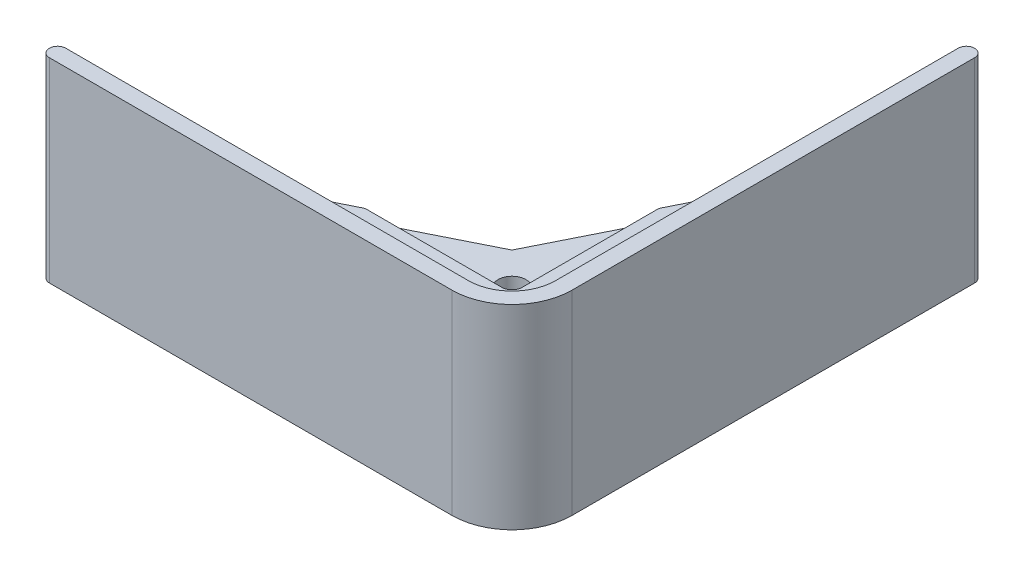
SolidWorks part; units mm, degrees
material "Nylon 101"
ref_plane "Front Plane" through (0, 0, 0) normal (0, 0, 1) x (1, 0, 0)
ref_plane "Top Plane" through (0, 0, 0) normal (0, 1, 0) x (1, 0, 0)
ref_plane "Right Plane" through (0, 0, 0) normal (1, 0, 0) x (0, 0, -1)
sketch "Sketch1" plane through (0, 0, 0) normal (0, 1, 0) x (1, 0, 0)
  line L0 (0, -18.542) -> (-127, -18.542)
  line L1 (18.542, 0) -> (18.542, 127)
  line L2 (-127, -18.542) -> (-127, -13.462)
  line L3 (-127, -13.462) -> (0, -13.462)
  line L4 (13.462, 0) -> (13.462, 127)
  line L5 (13.462, 127) -> (18.542, 127)
  line L6 (-6.0067, 12.0476) -> (-57.1711, -13.462)
  line L7 (-12.0476, 6.0067) -> (13.462, 57.1711)
  circle A0 centre (0, 0) radius 4.2862
  arc A1 (0, -18.542) -> (18.542, 0) centre (0, 0) ccw
  circle A2 centre (0, 0) radius 13.462
  dimension "D1" = 8.5725
  dimension "D4" = 5.08
  dimension "D5" = 127
  dimension "D6" = 26.5
  dimension "D3" = 13.462
extrude "Boss-Extrude1" add sketch "Sketch1" along normal blind 50.292 contours A2 L3 L2 L0 A1 L1 L5 L4 | A2 A0 | A2 L3 | A2 L4 L7 | A2 L6 L7 region at (-63.5, 0, 16.4837) region at (-26.4429, 0, 6.2746) region at (-11.1237, 0, 6.8835) region at (6.2746, 0, -26.4429) region at (-9.6262, 0, -9.6262)
fillet "Fillet2" radius 2.54 4 edges at (13.462, 25.146, -127) (18.542, 25.146, -127) (-127, 25.146, 13.462) (-127, 25.146, 18.542)
ref_plane "Plane1" through (0, 25.146, 0) normal (0, 1, 0) x (1, 0, 0)
sketch "Sketch7" plane through (0, 50.292, 0) normal (0, 1, 0) x (1, 0, 0)
  line L1 (5.08, -5.08) -> (-40.3594, -5.08)
  line L2 (5.08, -5.08) -> (5.08, 40.3594)
  line L3 (5.08, 40.3594) -> (-40.3594, 40.3594)
  line L4 (-40.3594, -5.08) -> (-40.3594, 40.3594)
  line L6 (-10.0378, 10.0378) -> (-57.1711, -13.462) construction
  circle A1 centre (0, 0) radius 4.2862 construction
  dimension "D1" = 5.08
  dimension "D2" = 5.08
extrude "Cut-Extrude3" cut sketch "Sketch7" against normal blind 3.556
fillet "Fillet9" radius 3.175 3 edges at (5.08, 48.514, -40.3594) (5.08, 48.514, 5.08) (-40.3594, 48.514, 5.08)
sketch "Sketch8" plane through (0, 25.146, 0) normal (0, 1, 0) x (1, 0, 0)
  line L0 (0, -13.462) -> (-124.46, -13.462)
  line L9 (-124.46, -18.542) -> (0, -18.542)
  line L10 (13.462, 57.1711) -> (5.4136, 41.0284)
  line L11 (5.08, 39.6118) -> (5.08, -1.905)
  line L12 (1.905, -5.08) -> (-39.6118, -5.08)
  line L13 (-41.0284, -5.4136) -> (-57.1711, -13.462)
  line L14 (-57.1711, -13.462) -> (-124.46, -13.462)
  line L16 (-124.46, -18.542) -> (0, -18.542)
  line L18 (18.542, 0) -> (18.542, 124.46)
  line L19 (13.462, 124.46) -> (13.462, 57.1711)
  line L29 (13.462, 124.46) -> (13.462, 0)
  line L30 (18.542, 0) -> (18.542, 124.46)
  arc A0 (0, -13.462) -> (13.462, 0) centre (0, 0) ccw
  arc A5 (-124.46, -13.462) -> (-127, -16.002) centre (-124.46, -16.002) ccw
  arc A7 (-124.46, -13.462) -> (-127, -16.002) centre (-124.46, -16.002) ccw
  arc A9 (5.4136, 41.0284) -> (5.08, 39.6118) centre (8.255, 39.6118) ccw
  arc A10 (1.905, -5.08) -> (5.08, -1.905) centre (1.905, -1.905) ccw
  arc A11 (-39.6118, -5.08) -> (-41.0284, -5.4136) centre (-39.6118, -8.255) ccw
  arc A16 (-127, -16.002) -> (-124.46, -18.542) centre (-124.46, -16.002) ccw
  arc A27 (-127, -16.002) -> (-124.46, -18.542) centre (-124.46, -16.002) ccw
  arc A29 (0, -18.542) -> (18.542, 0) centre (0, 0) ccw
  arc A31 (0, -18.542) -> (18.542, 0) centre (0, 0) ccw
  arc A32 (18.542, 124.46) -> (16.002, 127) centre (16.002, 124.46) ccw
  arc A33 (18.542, 124.46) -> (16.002, 127) centre (16.002, 124.46) ccw
  arc A34 (16.002, 127) -> (13.462, 124.46) centre (16.002, 124.46) ccw
  arc A35 (16.002, 127) -> (13.462, 124.46) centre (16.002, 124.46) ccw
  dimension "D1" = 0
extrude "Boss-Extrude2" add sketch "Sketch8" along normal mid plane 60.325
sketch "Sketch9" plane through (0, -5.0165, 0) normal (0, -1, 0) x (1, 0, 0)
  line L0 (-8.2875, 13.462) -> (7.112, 13.462)
  line L1 (-57.1711, 13.462) -> (0, 13.462) construction
  line L2 (13.462, -7.7751) -> (13.462, 7.112)
  line L3 (13.462, 0) -> (13.462, -57.1711) construction
  arc A0 (7.112, 13.462) -> (13.462, 7.112) centre (7.112, 7.112) cw
  arc A1 (13.462, 0) -> (0, 13.462) centre (0, 0) ccw construction
  arc A2 (13.462, 0) -> (0, 13.462) centre (0, 0) ccw
  arc M4 (0, 13.462) -> (13.462, 0) centre (0, 0) cw
  dimension "D1" = 6.35
extrude "Cut-Extrude4" cut sketch "Sketch9" against normal up to surface (5.0165 mm away) contours A0 L0 L2 M4 region at (10.0004, -5.0165, 10.0004) up to face at (0, 0, 4.2862)
equation "\"D1@Sketch1\"=.3125+0.025"
